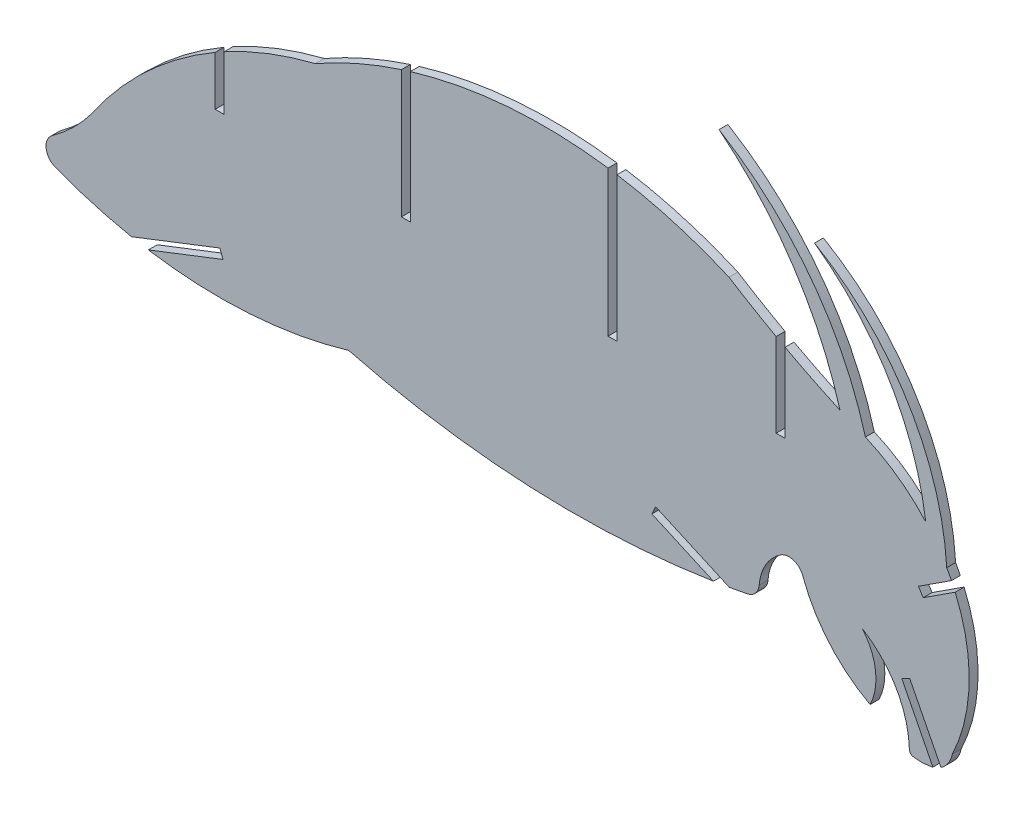
SolidWorks part; units mm, degrees
ref_plane "Front Plane" through (0, 0, 0) normal (0, 0, 1) x (1, 0, 0)
ref_plane "Top Plane" through (0, 0, 0) normal (0, 1, 0) x (1, 0, 0)
ref_plane "Right Plane" through (0, 0, 0) normal (1, 0, 0) x (0, 0, -1)
sketch "Sketch1" plane through (0, 0, 0) normal (0, 0, 1) x (1, 0, 0)
  line L0 (237.2231, 54.4268) -> (228.2293, 48.5965) construction
  line L1 (231.6947, 24.2639) -> (226.3223, 34.8264)
  line L2 (230.3104, 23.6241) -> (224.964, 34.1355)
  line L3 (233.4867, 52.9128) -> (227.8148, 49.2359)
  line L4 (226.3223, 34.8264) -> (224.964, 34.1355)
  line L5 (234.1335, 51.5159) -> (228.6438, 47.9571)
  line L7 (227.8148, 49.2359) -> (228.6438, 47.9571)
  line L8 (237.6376, 53.7874) -> (228.6438, 47.9571) construction
  line L9 (236.8086, 55.0662) -> (227.8148, 49.2359) construction
  line L10 (107.2121, 68.2316) -> (107.2121, 59.7772)
  line L11 (139.1639, 81.6517) -> (139.1639, 59.7772)
  line L12 (174.5957, 84.7433) -> (174.5957, 59.7772)
  line L13 (203.4266, 74.1394) -> (203.4266, 59.7772)
  line L14 (108.7361, 69.0882) -> (108.7361, 59.7772)
  line L15 (140.6879, 82.1272) -> (140.6879, 59.7772)
  line L16 (176.1197, 84.5159) -> (176.1197, 59.7772)
  line L17 (204.9506, 73.3125) -> (204.9506, 59.7772)
  line L19 (107.2121, 59.7772) -> (108.7361, 59.7772)
  line L21 (139.1639, 59.7772) -> (140.6879, 59.7772)
  line L23 (174.5957, 59.7772) -> (176.1197, 59.7772)
  line L25 (203.4266, 59.7772) -> (204.9506, 59.7772)
  line L28 (195.381, 32.8692) -> (182.7417, 38.5237)
  line L29 (95.7472, 33.1637) -> (108.5598, 38.1489)
  line L30 (192.6639, 32.4152) -> (182.1193, 37.1326)
  line L31 (92.8632, 33.6768) -> (108.0072, 39.5692)
  line L33 (182.7417, 38.5237) -> (182.1193, 37.1326)
  line L35 (108.5598, 38.1489) -> (108.0072, 39.5692)
  arc A0 (233.635, 27.2134) -> (234.1335, 51.5159) centre (207.2358, 39.9112) ccw
  arc A1 (214.3748, 68.665) -> (204.9506, 73.3125) centre (279.1205, 211.8342) cw
  arc A2 (195.3348, 78.908) -> (176.1197, 84.5159) centre (163.6192, 5.9601) ccw
  arc A3 (124.3731, 75.1484) -> (108.7361, 69.0882) centre (139.9259, 11.8141) ccw
  arc A4 (86.0726, 48.5965) -> (79.2546, 41.8834) centre (60.9319, 67.3112) cw
  arc A5 (79.8234, 37.4536) -> (92.8632, 33.6768) centre (107.9741, 110.2467) ccw
  arc A6 (130.129, 35.4105) -> (192.6639, 32.4152) centre (168.6178, 184.675) ccw
  arc A7 (200.5059, 35.739) -> (204.1886, 42.0868) centre (208.9587, 35.0771) cw
  arc A8 (208.0045, 40.8553) -> (213.2637, 32.3324) centre (231.2402, 49.3091) ccw
  arc A9 (233.635, 27.2134) -> (231.6947, 24.2639) centre (229.0845, 28.094) cw
  arc A10 (229.4896, 23.4768) -> (226.9064, 23.4874) centre (228.2293, 31.1225) cw
  arc A11 (226.2747, 24.2191) -> (226.9064, 23.4874) centre (227.0365, 24.2382) ccw
  arc A12 (230.3104, 23.6241) -> (229.4896, 23.4768) centre (229.0845, 28.094) cw
  arc A13 (79.2546, 41.8834) -> (79.8234, 37.4536) centre (80.7396, 39.8227) ccw
  arc A14 (204.1886, 42.0868) -> (208.0045, 40.8553) centre (205.6176, 39.9869) cw
  arc A15 (198.4654, 33.4454) -> (200.5059, 35.739) centre (197.9736, 35.9373) ccw
  arc A16 (203.4266, 74.1394) -> (195.3348, 78.908) centre (279.1205, 211.8342) cw
  arc A17 (174.5957, 84.7433) -> (140.6879, 82.1272) centre (163.6192, 5.9601) ccw
  arc A18 (139.1639, 81.6517) -> (124.3731, 75.1484) centre (163.6192, 5.9601) ccw
  arc A19 (107.2121, 68.2316) -> (86.0726, 48.5965) centre (139.9259, 11.8141) ccw
  arc A20 (95.7472, 33.1637) -> (130.129, 35.4105) centre (107.9741, 110.2467) ccw
  arc A21 (195.381, 32.8692) -> (198.4654, 33.4454) centre (168.6178, 184.675) ccw
  arc A22 (233.4867, 52.9128) -> (232.6808, 54.4268) centre (207.2358, 39.9112) ccw
  arc A23 (213.2637, 32.3324) -> (219.5382, 27.5278) centre (231.2402, 49.3091) ccw
  arc A24 (232.6808, 54.4268) -> (210.0105, 91.3149) centre (186.9413, 51.7269) ccw
  arc A25 (210.0105, 91.3149) -> (229.0845, 59.425) centre (182.6194, 53.2826) cw
  arc A26 (218.7352, 66.8541) -> (193.6314, 99.9802) centre (164.6318, 51.9284) ccw
  arc A27 (193.6314, 99.9802) -> (214.3748, 68.665) centre (154.7033, 51.666) cw
  arc A28 (229.0845, 59.425) -> (218.7352, 66.8541) centre (207.2358, 39.9112) ccw
  arc A29 (226.2747, 24.2191) -> (218.1956, 38.1489) centre (209.5041, 23.8002) ccw
  arc A30 (218.1956, 38.1489) -> (219.5382, 27.5278) centre (210.8457, 31.8244) cw
  point P26 (231.9194, 23.8222)
  point P28 (230.561, 23.1313)
  dimension "D3" = 2.54
  dimension "D4" = 0.762
  dimension "D1" = 0.762
  dimension "D2" = 0.762
sheet metal parameters "Sheet-Metal1" thickness 1.524 parameters "D1"=76.2
base flange "Base-Flange1" sketch "Sketch1" thickness 1.524 reverse thickness direction no parameters "D1"=76.2
flat pattern "Flat-Pattern1" [suppressed]
sketch "Bend-Lines1" plane through (0, 0, 0) normal (0, 1, 0) x (1, 0, 0)
sketch3d "Bounding-Box1" [suppressed]
  line L0 (147.1705, 63.4891, 0) -> (-10.4213, 52.1602, 0) construction
  line L1 (151.2978, 6.0746, 0) -> (-6.294, -5.2542, 0) construction
  line L2 (147.1705, 63.4891, 0) -> (151.2978, 6.0746, 0) construction
  line L3 (-10.4213, 52.1602, 0) -> (-6.294, -5.2542, 0) construction
